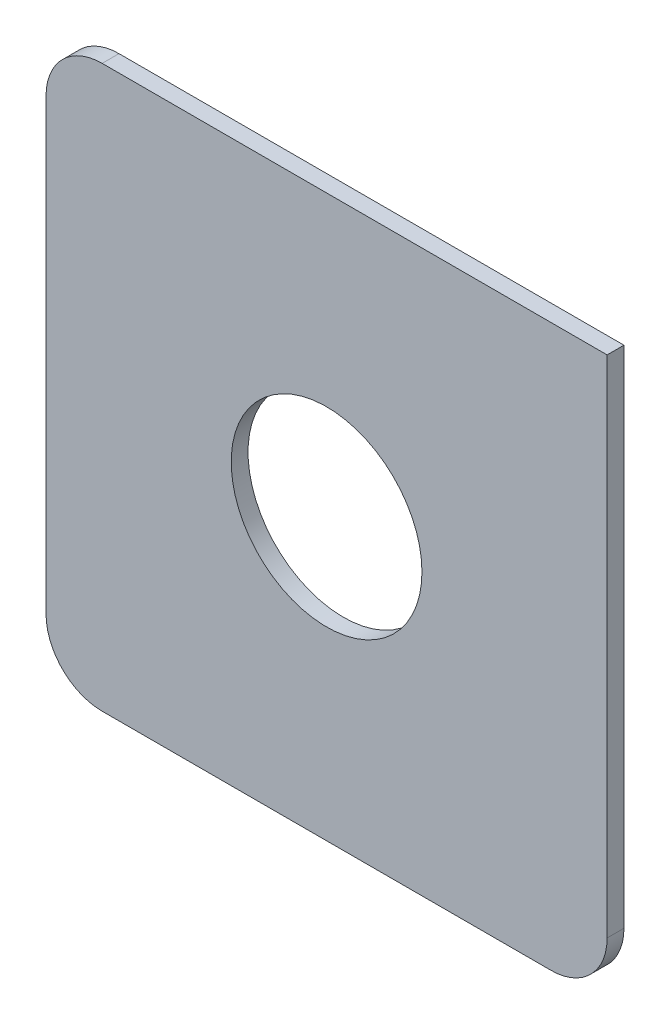
SolidWorks part; units mm, degrees
ref_plane "Plan de face" through (0, 0, 0) normal (0, 0, 1) x (1, 0, 0)
ref_plane "Plan de dessus" through (0, 0, 0) normal (0, 1, 0) x (1, 0, 0)
ref_plane "Plan de droite" through (0, 0, 0) normal (1, 0, 0) x (0, 0, -1)
sketch "Esquisse1" plane through (0, 0, 0) normal (0, 0, 1) x (1, 0, 0)
  line L0 (0, 0) -> (0, 100)
  line L1 (0, 100) -> (100, 100)
  line L2 (100, 100) -> (100, 0)
  line L3 (100, 0) -> (0, 0)
  dimension "D1" = 100
  dimension "D2" = 100
extrude "Boss.-Extru.1" add sketch "Esquisse1" along normal blind 3
fillet "Congé1" radius 10 3 edges at (100, 0, 1.5) (0, 0, 1.5) (0, 100, 1.5)
sketch "Esquisse2" plane through (0, 0, 3) normal (0, 0, 1) x (1, 0, 0)
  line L1 (0, 50) -> (73.6391, 50) construction
  line L2 (0, 90) -> (0, 10) construction
  line L3 (50, 0) -> (50, 72.7581) construction
  line L4 (10, 0) -> (90, 0) construction
  circle A0 centre (50, 50) radius 17
  point P10 (50, 50)
  dimension "D1" = 34
extrude "Enlèv. mat.-Extru.1" cut sketch "Esquisse2" against normal up to surface (3 mm away) up to face at (43.9898, 43.9898, 0)
